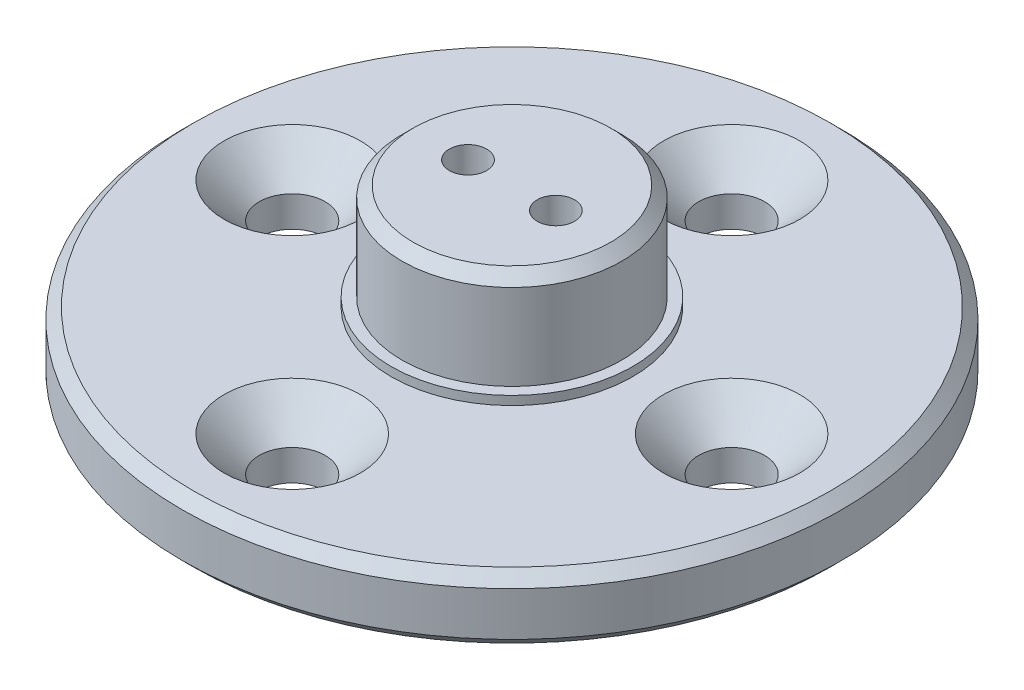
SolidWorks part; units mm, degrees
ref_plane "前视基准面" through (0, 0, 0) normal (0, 0, 1) x (1, 0, 0)
ref_plane "上视基准面" through (0, 0, 0) normal (0, 1, 0) x (1, 0, 0)
ref_plane "右视基准面" through (0, 0, 0) normal (1, 0, 0) x (0, 0, -1)
other "Configuration Table"
sketch "草图1" plane through (0, 0, 0) normal (0, 1, 0) x (1, 0, 0)
  line L0 (-21.98, 0) -> (22.6908, 0) construction
  line L1 (0, 22.7485) -> (0, -21.9381) construction
  circle A0 centre (0, 0) radius 15
  circle A1 centre (0, 10) radius 1.5
  circle A2 centre (10, 0) radius 1.5
  circle A3 centre (0, -10) radius 1.5
  circle A4 centre (-10, 0) radius 1.5
  point P15 (0, 0)
  dimension "D1" = 3
  dimension "D3" = 30
  dimension "D2" = 10
extrude "凸台-拉伸1" add sketch "草图1" along normal blind 3
sketch "草图2" plane through (0, 3, 0) normal (0, 1, 0) x (1, 0, 0)
  line L0 (0, 1.9211) -> (0, -1.7964) construction
  line L1 (-1.959, 0) -> (1.7076, 0) construction
  circle A1 centre (0, 0) radius 5
  circle A3 centre (2, 0) radius 0.85
  circle A4 centre (-2, 0) radius 0.85
  dimension "D1" = 10
  dimension "D2" = 1.7
  dimension "D3" = 4
extrude "凸台-拉伸2" add sketch "草图2" along normal blind 4.8
sketch "草图4" plane through (0, 3, 0) normal (0, 1, 0) x (1, 0, 0)
  circle A8 centre (0, 0) radius 5.5
  point P15 (0, 0)
  dimension "D1" = 11
extrude "凸台-拉伸3" add sketch "草图4" along normal blind 0.4
chamfer "倒角1" distance 0.5 angle 45 1 edges at (0, 7.8, 5)
chamfer "倒角3" distance 0.5 angle 45 2 edges at (0, 0, 15) (0, 3, 15)
chamfer "倒角4" distance 1.6 angle 45 4 edges at (10, 3, 1.5) (0, 3, 11.5) (-10, 3, 1.5) (0, 3, -8.5)
